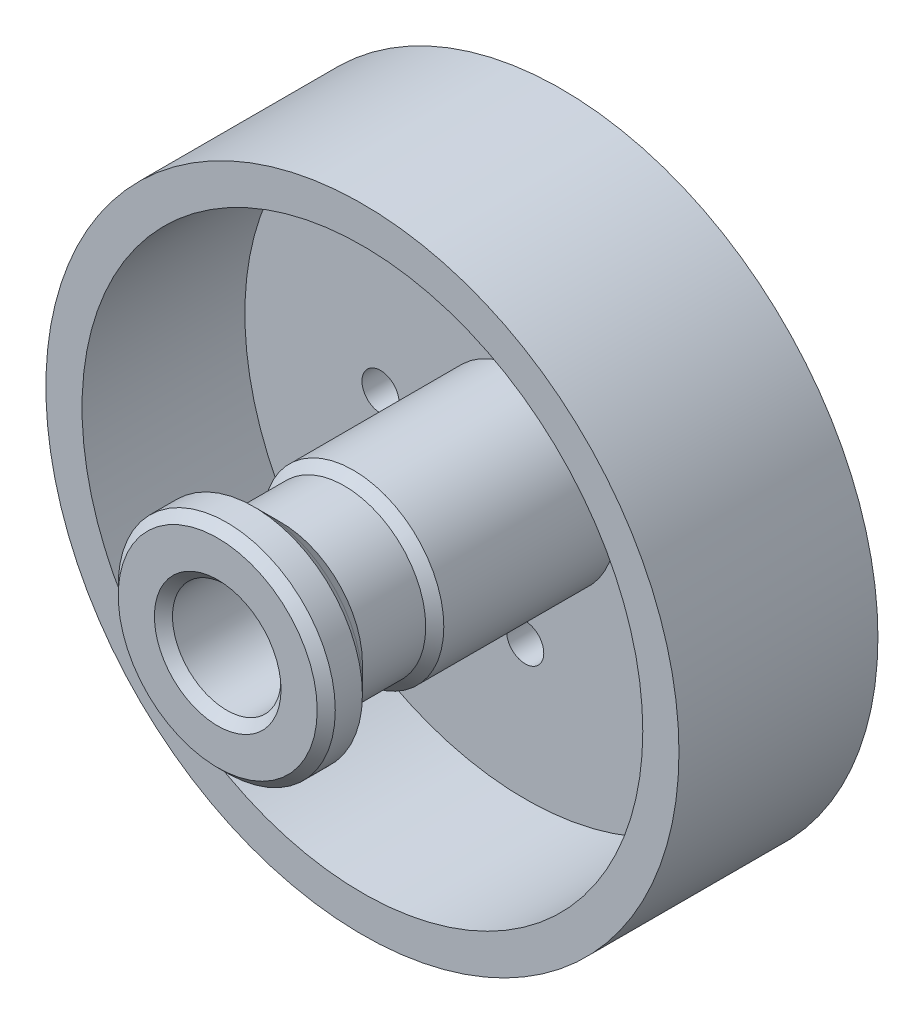
SolidWorks part; units mm, degrees
ref_plane "前视基准面" through (0, 0, 0) normal (0, 0, 1) x (1, 0, 0)
ref_plane "上视基准面" through (0, 0, 0) normal (0, 1, 0) x (1, 0, 0)
ref_plane "右视基准面" through (0, 0, 0) normal (1, 0, 0) x (0, 0, -1)
other "Configuration Table"
sketch "草图1" plane through (0, 0, 0) normal (0, 0, 1) x (1, 0, 0)
  circle A0 centre (0, 0) radius 17.5
  circle A1 centre (0, 0) radius 8 construction
  circle A2 centre (0, 0) radius 3
  circle A3 centre (0, 8) radius 0.5
  circle A4 centre (-8, 0) radius 0.5
  circle A5 centre (8, 0) radius 0.5
  circle A6 centre (0, -8) radius 0.5
  dimension "D1" = 35
  dimension "D2" = 16
  dimension "D3" = 6
  dimension "D4" = 1
  dimension "D5" = 1
  dimension "D6" = 1
  dimension "D7" = 1
extrude "凸台-拉伸1" add sketch "草图1" against normal blind 11
shell "抽壳1" thickness 2 removed face at (0.5, -8, 0)
sketch "草图2" plane through (0, 0, -9) normal (0, 0, 1) x (1, 0, 0)
  circle A0 centre (0, 0) radius 5
  circle A1 centre (0, 0) radius 12.5
  dimension "D1" = 10
  dimension "D2" = 25
extrude "切除-拉伸1" cut sketch "草图2" along normal blind 10
hole_wizard "M2.5 螺纹孔的螺纹孔钻头1" positions "草图3" profile "草图4" hole size "M2.5" standard "GB"
sketch "草图3" plane through (0, 0, -11) normal (0, 0, -1) x (-1, 0, 0)
  point P0 (0, 8)
  point P3 (8, 0)
  point P6 (0, -8)
  point P9 (-8, 0)
sketch "草图4" plane through (0, 8, -11) normal (1, 0, 0) x (0, 1, 0)
  line L0 (0, 0) -> (0, 10.6159)
  line L1 (0, 10.6159) -> (1.025, 10)
  line L2 (1.025, 10) -> (1.025, 0)
  line L5 (1.025, 0) -> (0, 0)
  line L10 (0, 10.6159) -> (-1.025, 10) construction
  line L11 (0, -6.35) -> (0, 107.95) construction
  dimension "孔直径" = 2.05
  dimension "孔深度" = 10
  dimension "导头角度" = 118
cosmetic thread "装饰螺纹线1" parameters "D2"=2.5
cosmetic thread "装饰螺纹线2" parameters "D2"=2.5
cosmetic thread "装饰螺纹线3" parameters "D2"=2.5
cosmetic thread "装饰螺纹线4" parameters "D2"=2.5
sketch "草图5" plane through (0, 0, 0) normal (0, 0, 1) x (1, 0, 0)
  circle A0 centre (0, 0) radius 4.5
  circle A1 centre (0, 0) radius 3
  dimension "D1" = 9
  dimension "D2" = 6
extrude "凸台-拉伸2" add sketch "草图5" along normal blind 8
sketch "草图6" plane through (0, 0, 8) normal (0, 0, 1) x (1, 0, 0)
  circle A0 centre (0, 0) radius 6
  circle A1 centre (0, 0) radius 3
  dimension "D1" = 12
  dimension "D2" = 6
extrude "凸台-拉伸3" add sketch "草图6" against normal blind 2.5
chamfer "倒角1" distance 0.5 angle 45 3 edges at (6, 0, 8) (3, 0, 8) (6, 0, 5.5)
chamfer "倒角2" distance 1 angle 45 2 edges at (4.5, 0, 5.5) (4.5, 0, 0)
